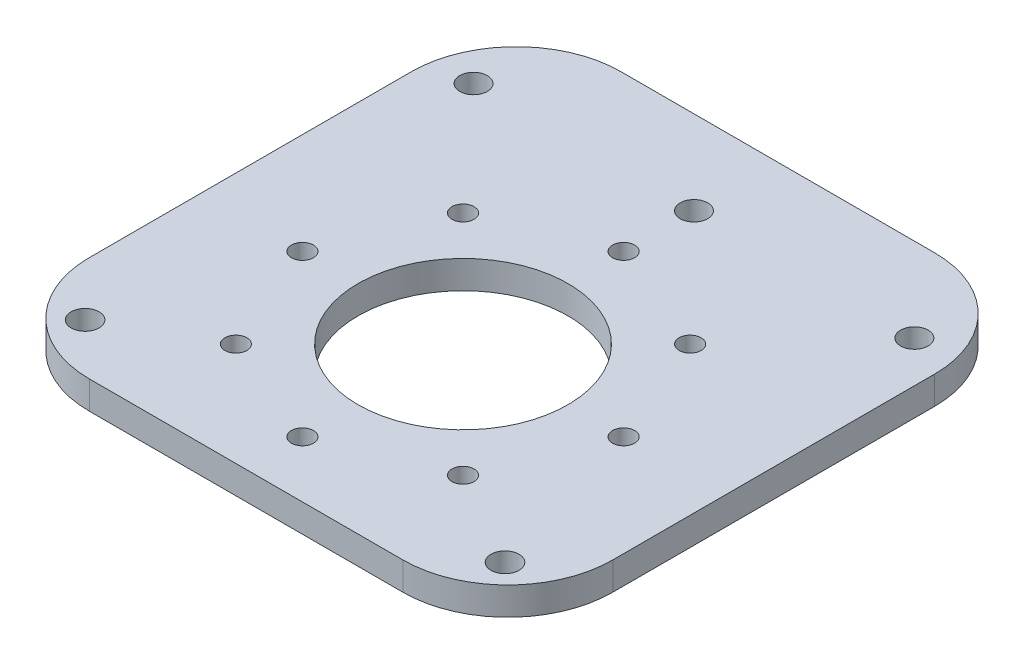
SolidWorks part; units mm, degrees
material "6061 Alloy"
ref_plane "Front Plane" through (0, 0, 0) normal (0, 0, 1) x (1, 0, 0)
ref_plane "Top Plane" through (0, 0, 0) normal (0, 1, 0) x (1, 0, 0)
ref_plane "Right Plane" through (0, 0, 0) normal (1, 0, 0) x (0, 0, -1)
sketch "Sketch2" plane through (0, 0, 0) normal (0, 1, 0) x (1, 0, 0)
  line L0 (0, 0) -> (0, 35.56) construction
  line L1 (-47.5, -60.96) -> (-47.5, 35.56)
  line L2 (47.5, -60.96) -> (47.5, 35.56)
  line L3 (-47.5, 35.56) -> (47.5, 35.56)
  line L4 (-47.5, -60.96) -> (47.5, -60.96)
  point P3 (47.5, -12.7)
  point P5 (0, 35.56)
  point P12 (0, -60.96)
  dimension "D1" = 96.52
  dimension "D2" = 95
  dimension "D3" = 12.7
extrude "Boss-Extrude3" add sketch "Sketch2" along normal blind 5.08
sketch "Sketch3" plane through (0, 5.08, 0) normal (0, 1, 0) x (1, 0, 0)
  line L0 (47.5, 35.56) -> (-47.5, 35.56) construction
  circle A1 centre (0, -21.59) radius 19.05
  dimension "D2" = 38.1
  dimension "D3" = 57.15
extrude "Cut-Extrude1" cut sketch "Sketch3" against normal through all
sketch "Sketch4" plane through (0, 5.08, 0) normal (0, 1, 0) x (1, 0, 0)
  line L0 (47.5, 35.56) -> (-47.5, 35.56) construction
  line L1 (0, 35.56) -> (0, 55.3884) construction
  point P0 (-40, 20.32)
  point P7 (40, 20.32)
  point P8 (0, 20.32)
  point P10 (0, 20.32)
  dimension "D1" = 15.24
  dimension "D2" = 80
hole_wizard "M6x1.0 Tapped Hole1" positions "Sketch4" profile "Sketch6" tap size "M6x1.0" standard "ANSI Metric"
sketch "Sketch6" plane through (-40, 5.08, -20.32) normal (1, 0, 0) x (0, 0, 1)
  line L0 (0, 0) -> (0, 6.5822)
  line L1 (0, 6.5822) -> (2.5, 5.08)
  line L2 (2.5, 5.08) -> (2.5, 0)
  line L5 (2.5, 0) -> (0, 0)
  line L10 (0, 6.5822) -> (-2.5, 5.08) construction
  line L11 (0, -6.35) -> (0, 107.95) construction
  dimension "Tap Drill Dia." = 5
  dimension "Tap Drill Depth" = 5.08
  dimension "Drill Angle" = 118
sketch "Sketch7" plane through (0, 5.08, 0) normal (0, 1, 0) x (1, 0, 0)
  line L0 (0, 0) -> (0, -60.96) construction
  line L1 (-47.5, -60.96) -> (47.5, -60.96) construction
  circle A2 centre (-38.1, -52.07) radius 2.54
  circle A3 centre (38.1, -52.07) radius 2.54
  dimension "D4" = 5.08
  dimension "D6" = 38.1
  dimension "D1" = 52.07
extrude "Cut-Extrude2" cut sketch "Sketch7" against normal blind 7.62
sketch "Sketch12" plane through (0, 5.08, 0) normal (0, 1, 0) x (1, 0, 0)
  line L0 (47.5, 35.56) -> (-47.5, 35.56) construction
  circle A0 centre (0, -21.59) radius 29.1465
  circle A1 centre (0, 7.5565) radius 2
  circle A2 centre (20.6097, -0.9803) radius 2
  circle A3 centre (29.1465, -21.59) radius 2
  circle A4 centre (20.6097, -42.1997) radius 2
  circle A5 centre (0, -50.7365) radius 2
  circle A6 centre (-20.6097, -42.1997) radius 2
  circle A7 centre (-29.1465, -21.59) radius 2
  circle A8 centre (-20.6097, -0.9803) radius 2
  point P25 (0, -21.59)
  dimension "D1" = 4
  dimension "D2" = 58.293
  dimension "D3" = 57.15
  dimension "D4" = 8
extrude "Cut-Extrude3" cut sketch "Sketch12" against normal through all contours A8 | A7 | A6 | A5 | A4 | A3 | A2 | A1
fillet "Fillet1" radius 19.05 4 edges at (47.5, 2.54, -35.56) (47.5, 2.54, 60.96) (-47.5, 2.54, 60.96) (-47.5, 2.54, -35.56)
